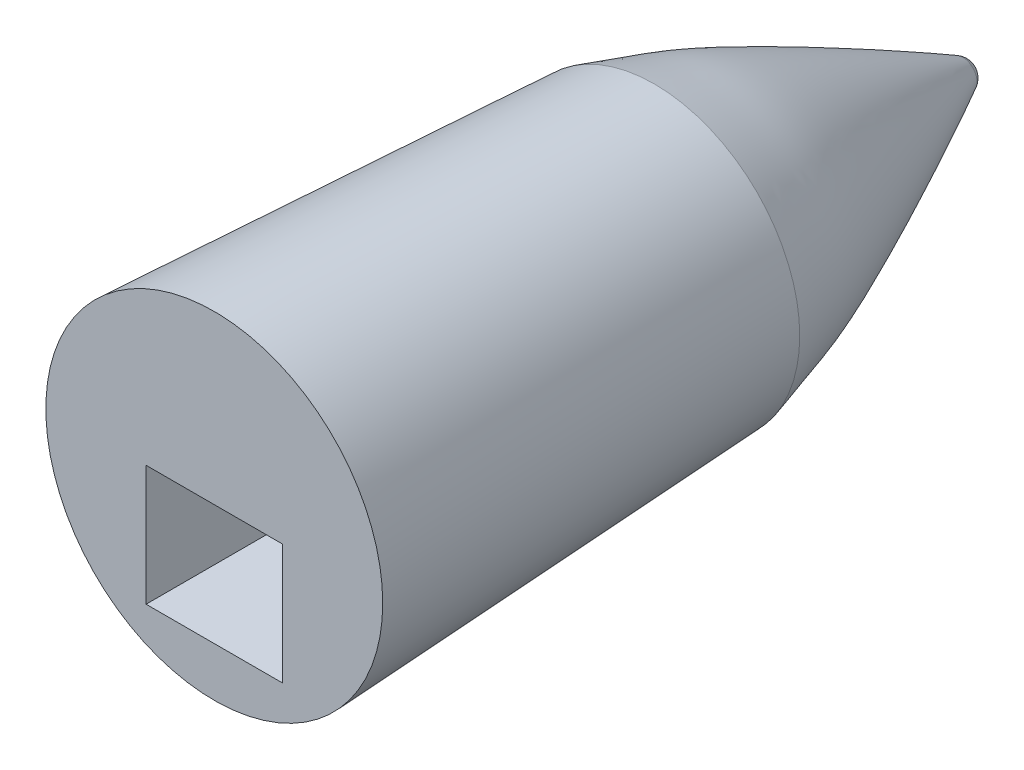
SolidWorks part; units mm, degrees
material "Свинец без примесей"
ref_plane "Спереди" through (0, 0, 0) normal (0, 0, 1) x (1, 0, 0)
ref_plane "Сверху" through (0, 0, 0) normal (0, 1, 0) x (1, 0, 0)
ref_plane "Справа" through (0, 0, 0) normal (1, 0, 0) x (0, 0, -1)
sketch "Эскиз1" plane through (0, 0, 0) normal (0, 1, 0) x (1, 0, 0)
  line L0 (0, 0) -> (0, 80) construction
  line L1 (0, 0) -> (-25, 0) construction
  line L2 (-21, 2) -> (-21, -18) construction
  line L5 (-21, -20) -> (0, -20)
  line L8 (-25, 0) -> (0, 80) construction
  line L10 (-21, 23.3035) -> (-21, -20)
  line L11 (0, 76.5095) -> (0, -20)
  line L12 (-2, -18) -> (-2, 66.8948) construction
  line L13 (-21, -18) -> (-2, -18) construction
  line L14 (0, -20) -> (0, 80) construction
  line L15 (-22.2796, 2) -> (-2, 66.8948) construction
  line L16 (-21.7437, -20) -> (0, -20) construction
  line L20 (-21, -18) -> (0, -18) construction
  line L21 (-21.7437, -20) -> (-23, -20) construction
  line L22 (-22.2796, 2) -> (-21, 2) construction
  line L23 (-23.0191, 2) -> (-21, 2) construction
  line L24 (-21, -18) -> (-21, -18) construction
  line L25 (-21, -18) -> (-21, -18) construction
  line L26 (-23, 0) -> (-23, -20) construction
  line L27 (-21, 2) -> (-21, -18) construction
  line L28 (-25, 0) -> (-23, 0) construction
  spline S0 degree 3 poles (-25, 0) (-25.3345, 19.1075) (-20.4075, 33.8926) (-15.3337, 51.5733) (-1.1082, 79.7902) (0, 80) knots 0 0 0 0 0.501806 0.601806 1 1 1 1 construction
  spline S1 degree 1 poles (-23.0191, 2) (1.1823, 78.3869) knots 0 0 1 1 construction
  spline S2 degree 3 poles (-23.0191, 2) (-23.0199, 2.538) (-23.0142, 3.6222) (-22.9746, 5.7238) (-22.8747, 8.2734) (-22.6809, 11.1999) (-22.3338, 14.9367) (-21.7512, 19.309) (-20.8698, 24.1215) (-19.8618, 28.543) (-18.781, 32.6183) (-17.6838, 36.3877) (-16.7941, 39.3248) (-16.14, 41.546) (-15.6355, 43.1976) (-15.0242, 45.0124) (-13.9372, 47.8862) (-11.955, 52.5312) (-8.9966, 58.9452) (-6.3405, 64.4155) (-4.2832, 68.5097) (-2.819, 71.3511) (-1.4799, 73.8732) (-0.5075, 75.6326) (0.1572, 76.7835) (0.5917, 77.5048) (0.8871, 77.967) (1.0813, 78.2501) (1.1449, 78.3375) (1.1823, 78.3869) knots 0.017702 0.017702 0.017702 0.017702 0.032587 0.047472 0.077243 0.107013 0.136783 0.196324 0.255865 0.315406 0.374947 0.434488 0.494029 0.523799 0.553569 0.58334 0.61311 0.672651 0.732192 0.791733 0.821503 0.851274 0.881044 0.910815 0.9257 0.940585 0.95547 0.962913 0.970355 0.970355 0.970355 0.970355 only from (-21, 23.3035) to (0, 76.5095)
  dimension "D1" = 25
  dimension "D2" = 21
  dimension "D4" = 2
  dimension "D5" = 100
revolve "Повернуть1" add sketch "Эскиз1" angle 360 about L11
sketch "Эскиз2" plane through (0, 0, 0) normal (0, 1, 0) x (1, 0, 0)
  line L0 (21, -20) -> (21, 66.972)
  line L1 (21, -20) -> (16.442, 66.972)
  line L2 (21, 66.972) -> (16.442, 66.972)
  dimension "D1" = 3
ref_axis "Ось1" through (0, 0, 20) along (0, 0, -1)
revolve "Вырез-Повернуть1" cut sketch "Эскиз2" angle 360 about axis through (0, 0, 20) along (0, 0, -1)
sketch "Эскиз3" plane through (0, 0, 0) normal (0, 1, 0) x (1, 0, 0)
  line L0 (0, 76.5095) -> (0, 74.3882)
  line L5 (1.7622, 73.3341) -> (4.0259, 73.3341)
  line L7 (4.0259, 73.3341) -> (4.0259, 76.5095)
  line L8 (4.0259, 76.5095) -> (0, 76.5095)
  arc A2 (1.7622, 73.3341) -> (0, 74.3882) centre (0, 72.3882) ccw
revolve "Вырез-Повернуть2" cut sketch "Эскиз3" angle 360 about L0
sketch "Эскиз4" plane through (0, 0, 20) normal (0, 0, 1) x (1, 0, 0)
  line L1 (8.5, 0.1365) -> (-8.5, 0.1365)
  line L2 (8.5, 0.1365) -> (8.5, -14.8635)
  line L3 (8.5, -14.8635) -> (-8.5, -14.8635)
  line L4 (-8.5, 0.1365) -> (-8.5, -14.8635)
  line L5 (8.5, 0.1365) -> (-8.5, -14.8635) construction
  line L6 (8.5, -14.8635) -> (-8.5, 0.1365) construction
  point P0 (0, -7.3635)
  dimension "D1" = 15
  dimension "D2" = 17
extrude "Вырез-Вытянуть1" cut sketch "Эскиз4" against normal blind 30 contours L2 L1 L4 L3
sketch "Эскиз5" plane through (0, -14.8635, 0) normal (0, 1, 0) x (1, 0, 0)
  line L1 (8.5, 10) -> (-8.5, 10)
  line L2 (8.5, 10) -> (8.5, -2)
  line L3 (8.5, -2) -> (-8.5, -2)
  line L4 (-8.5, 10) -> (-8.5, -2)
  line L5 (-8.5, 10) -> (-8.5, -20) construction
  dimension "D1" = 12
  dimension "D2" = 0
extrude "Вырез-Вытянуть2" cut sketch "Эскиз5" along normal blind 25
